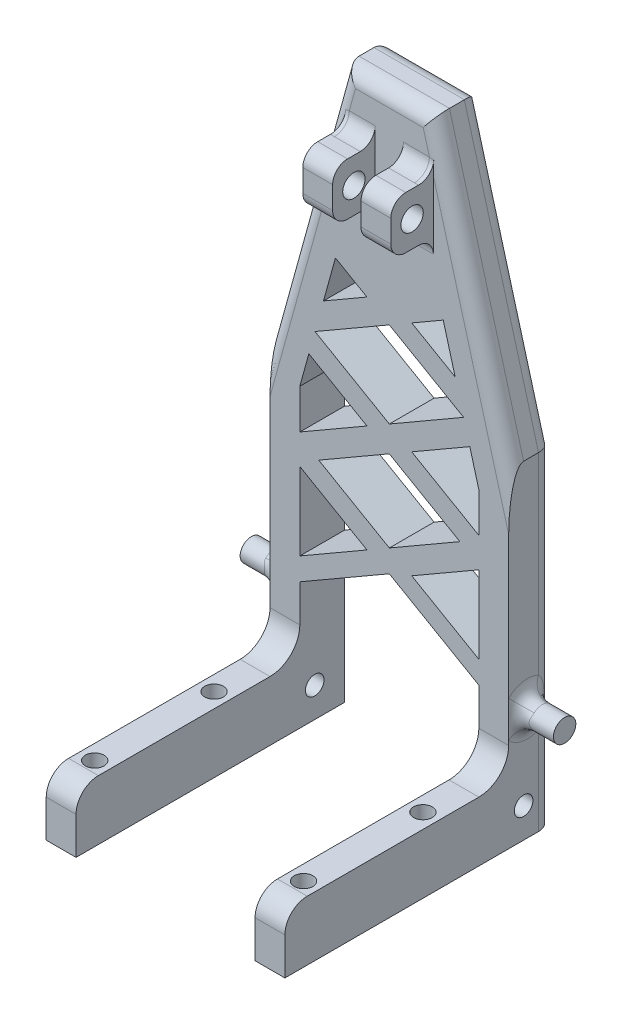
SolidWorks part; units mm, degrees
ref_plane "Front Plane" through (0, 0, 0) normal (0, 0, 1) x (1, 0, 0)
ref_plane "Top Plane" through (0, 0, 0) normal (0, 1, 0) x (1, 0, 0)
ref_plane "Right Plane" through (0, 0, 0) normal (1, 0, 0) x (0, 0, -1)
sketch "Sketch1" plane through (0, 0, 0) normal (0, 1, 0) x (1, 0, 0)
  line L0 (0, 0) -> (0, 15) construction
  line L1 (-12, -15) -> (12, -15) construction
  line L2 (-12, -15) -> (-12, 15) construction
  line L3 (-12, 15) -> (12, 15) construction
  line L4 (12, -15) -> (12, 15) construction
  line L5 (-12, -15) -> (12, 15) construction
  line L6 (-12, 15) -> (12, -15) construction
  line L7 (-12, -15) -> (-16, -15)
  line L8 (-12, -15) -> (-12, 15)
  line L9 (-12, 15) -> (-16, 15)
  line L10 (-16, -15) -> (-16, 15)
  line L11 (12, 15) -> (16, 15)
  line L12 (16, -15) -> (16, 15)
  line L13 (12, -15) -> (16, -15)
  line L14 (12, -15) -> (12, 15)
  line L15 (-14, -15) -> (-14, 15) construction
  circle A0 centre (-14, -10.5) radius 1.25
  circle A1 centre (-14, 5.5) radius 1.25
  circle A2 centre (14, -10.5) radius 1.25
  circle A3 centre (14, 5.5) radius 1.25
  point P0 (0, 0)
  dimension "D5" = 2.5
  dimension "D7" = 2.5
  dimension "D1" = 24
  dimension "D2" = 30
  dimension "D3" = 4
  dimension "D4" = 4.5
  dimension "D6" = 16
extrude "Boss-Extrude1" add sketch "Sketch1" along normal blind 8 contours A1 | A0 | L14 L13 L12 L11 A2 A3 | L8 L7 L10 L9
ref_plane "Plane1" through (0, 0, 0) normal (-1, 0, 0) x (0, 0, 1)
sketch "Sketch3" plane through (0, 0, 0) normal (-1, 0, 0) x (0, 0, 1)
  line L1 (-15, 0) -> (-21, 0)
  line L2 (-15, 0) -> (-15, 80)
  line L3 (-15, 80) -> (-21, 80)
  line L4 (-21, 0) -> (-21, 80)
  dimension "D1" = 80
  dimension "D2" = 6
extrude "Boss-Extrude2" add sketch "Sketch3" against normal up to surface and the other way up to surface
sketch "Sketch4" plane through (0, 0, -15) normal (0, 0, 1) x (1, 0, 0)
  line L0 (-12, 8) -> (-12, 0) construction
  line L1 (-12, 39.7004) -> (12, 39.7004)
  line L2 (-12, 39.7004) -> (-12, 0)
  line L3 (-12, 0) -> (12, 0)
  line L4 (12, 39.7004) -> (12, 0)
  line L5 (0, 80) -> (0, 0)
  line L6 (16, 80) -> (-16, 80) construction
  line L7 (-6.0607, 80) -> (6.0607, 80)
  line L8 (-6.0607, 80) -> (-16, 44)
  line L9 (-16, 8) -> (-16, 80) construction
  line L10 (6.0607, 80) -> (16, 44)
  line L11 (16, 80) -> (16, 8) construction
  line L12 (-6.0607, 80) -> (-16, 80)
  line L13 (-16, 80) -> (-16, 44)
  line L14 (6.0607, 80) -> (16, 80)
  line L15 (16, 80) -> (16, 44)
  line L16 (-2.8798, 72.734) -> (2.8798, 72.734)
  line L17 (-2.8798, 72.734) -> (-12, 39.7004)
  line L18 (2.8798, 72.734) -> (12, 39.7004)
  line L19 (-12, 39.7004) -> (12, 39.7004)
  line L20 (-12, 20) -> (-3, 25.1962)
  line L21 (-3, 25.1962) -> (-12, 30.3923)
  line L22 (-12, 32.3923) -> (12, 32.3923) construction
  line L23 (-3, 39.5885) -> (-12, 34.3923)
  line L24 (-12, 44.7846) -> (-3, 39.5885)
  line L25 (12, 20) -> (3, 25.1962)
  line L26 (3, 25.1962) -> (12, 30.3923)
  line L27 (12, 44.7846) -> (3, 39.5885)
  line L28 (3, 39.5885) -> (12, 34.3923)
  line L29 (-12, 17) -> (0, 23.9282)
  line L30 (0, 26.9282) -> (-9.4641, 32.3923)
  line L31 (-9.4641, 32.3923) -> (0, 37.8564)
  line L32 (0, 41.3205) -> (-9.9644, 47.0734)
  line L33 (-9.9644, 47.0734) -> (0, 52.8264)
  line L34 (0, 52.8264) -> (0, 56.2864)
  line L35 (0, 56.2864) -> (-6.4005, 59.9817)
  line L36 (-8.8266, 51.1944) -> (-3.0036, 54.5564)
  line L37 (-3.0036, 54.5564) -> (-7.2254, 56.9939)
  line L38 (0, 56.2864) -> (6.4005, 59.9817)
  line L39 (3.0036, 54.5564) -> (7.2254, 56.9939)
  line L40 (8.8266, 51.1944) -> (3.0036, 54.5564)
  line L41 (9.9644, 47.0734) -> (0, 52.8264)
  line L42 (0, 41.3205) -> (9.9644, 47.0734)
  line L43 (9.4641, 32.3923) -> (0, 37.8564)
  line L44 (0, 26.9282) -> (9.4641, 32.3923)
  line L45 (12, 17) -> (0, 23.9282)
  point P4 (0, 0)
  point P14 (0, 80)
  point P27 (0, 72.734)
  line M5 (12, 0) -> (12, 8)
  line M7 (16, 8) -> (16, 80)
  line M8 (16, 80) -> (-16, 80)
  line M9 (-16, 80) -> (-16, 8)
  line M11 (-12, 8) -> (-12, 0)
  line M12 (-12, 0) -> (12, 0)
  dimension "D1" = 5
  dimension "D2" = 60
  dimension "D3" = 60
  dimension "D4" = 20
  dimension "D5" = 3
  dimension "D6" = 2
  dimension "D7" = 3
  dimension "D8" = 3
  dimension "D9" = 3
  dimension "D10" = 60
  dimension "D11" = 120
  dimension "D12" = 3
  dimension "D13" = 3
  dimension "D14" = 3.46
extrude "Cut-Extrude2" cut sketch "Sketch4" against normal blind 10 contours L29 L2 L5 M11 M12 | L4 L45 L5 L3 M5 | L20 L21 L2 | L26 L25 L4 | L5 L22 L43 | L31 L22 L5 | L22 L30 L5 | L22 L5 L44 | L27 L28 L4 L19 | L24 L1 L2 L23 | L24 L17 L1 | L18 L27 L19 | L5 L42 L41 | L33 L32 L5 | L36 L37 L17 | L40 L18 L39 | L8 M8 M9 | L10 M8 M7
sketch "Sketch5" plane through (-16, 0, 0) normal (-1, 0, 0) x (0, 0, 1)
  line L0 (-15, 8) -> (-19, 0)
  line L1 (15, 0) -> (-21, 0) construction
  line L2 (-21, 44) -> (-21, 0) construction
  circle A0 centre (-17, 4) radius 1.25
  dimension "D1" = 2.5
  dimension "D2" = 2
extrude "Cut-Extrude3" cut sketch "Sketch5" against normal through all contours L0 A0 | L0 A0
sketch "Sketch6" plane through (0, 0, -15) normal (0, 0, 1) x (1, 0, 0)
  line L0 (0, 52.8264) -> (0, 80)
  line L1 (6.0607, 80) -> (-6.0607, 80) construction
  line L2 (1.9, 66) -> (1.9, 73)
  line L3 (-5.9, 66) -> (-1.9, 66)
  line L4 (-5.9, 66) -> (-5.9, 73)
  line L5 (-5.9, 73) -> (-1.9, 73)
  line L6 (-1.9, 66) -> (-1.9, 73)
  line L7 (5.9, 73) -> (1.9, 73)
  line L8 (5.9, 66) -> (5.9, 73)
  line L9 (5.9, 66) -> (1.9, 66)
  dimension "D1" = 1.9
  dimension "D2" = 7
  dimension "D3" = 4
  dimension "D4" = 7
extrude "Boss-Extrude3" add sketch "Sketch6" along normal blind 5.7 contours L3 L6 L5 L4 | L9 L8 L7 L2
sketch "Sketch7" plane through (5.9, 0, 0) normal (1, 0, 0) x (0, 0, -1)
  line L0 (15, 66) -> (9.3, 73)
  line L1 (9.3, 73) -> (15, 73)
  line L2 (15, 73) -> (9.3, 66)
  circle A0 centre (12.15, 69.5) radius 1.5
  dimension "D1" = 3
extrude "Cut-Extrude4" cut sketch "Sketch7" against normal through all contours L0 A0 L2 | L2 A0 L0 | L0 A0 L2 | L2 A0 L0
fillet "Fillet4" radius 2 5 edges at (0, 80, -21) (-11.0304, 62, -21) (-16, 22, -21) (16, 22, -21) (11.0304, 62, -21)
fillet "Fillet2" radius 4 2 edges at (-14, 8, -15) (14, 8, -15)
fillet "Fillet3" radius 3 2 edges at (14, 8, 15) (-14, 8, 15)
fillet "Fillet5" radius 2 3 edges at (-11.0304, 62, -15) (11.0304, 62, -15) (0, 80, -15)
fillet "Fillet6" radius 2 4 edges at (3.9, 66, -9.3) (3.9, 73, -9.3) (-3.9, 73, -9.3) (-3.9, 66, -9.3)
fillet "Fillet7" radius 2 4 edges at (3.9, 73, -15) (-3.9, 73, -15) (3.9, 66, -15) (-3.9, 66, -15)
sketch "Sketch8" plane through (-16, 0, 0) normal (-1, 0, 0) x (0, 0, 1)
  line L1 (-19, 44) -> (-19, 0) construction
  line L2 (15, 0) -> (-19, 0) construction
  circle A0 centre (-17.5, 15) radius 1.5
  dimension "D1" = 3
  dimension "D2" = 15
extrude "Boss-Extrude4" add sketch "Sketch8" along normal blind 5
mirror "Mirror3" about plane through (0, 0, 0) normal (-1, 0, 0) of "Boss-Extrude4"
fillet "Fillet8" radius 2 2 edges at (-16, 15, -16) (16, 15, -16)
